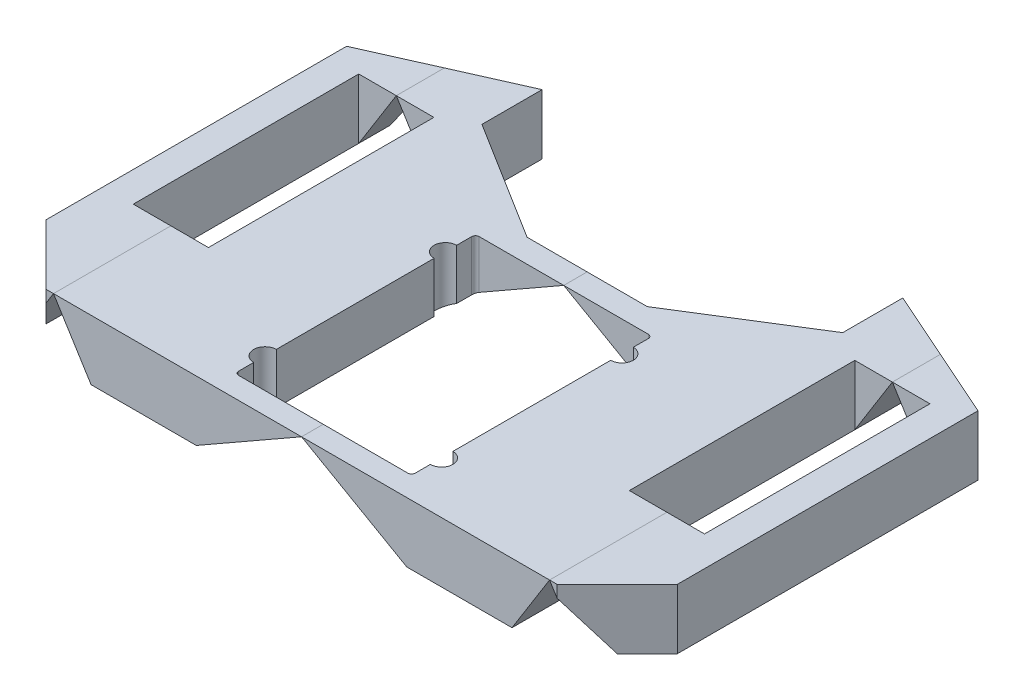
SolidWorks part; units mm, degrees
material "Polyurethane Foam Rigid"
ref_plane "Front Plane" through (0, 0, 0) normal (0, 0, 1) x (1, 0, 0)
ref_plane "Top Plane" through (0, 0, 0) normal (0, 1, 0) x (1, 0, 0)
ref_plane "Right Plane" through (0, 0, 0) normal (1, 0, 0) x (0, 0, -1)
sketch "Sketch1" plane through (0, 0, 0) normal (0, 1, 0) x (1, 0, 0)
  line L28 (52.9999, -138.966) -> (116.4999, -138.966) construction
  line L29 (52.9999, -138.966) -> (52.9999, -329.466) construction
  line L30 (52.9999, -329.466) -> (116.4999, -329.466) construction
  line L31 (116.4999, -138.966) -> (116.4999, -329.466) construction
  line L32 (472.0999, -138.966) -> (472.0999, -329.466) construction
  line L33 (535.5999, -329.466) -> (472.0999, -329.466) construction
  line L34 (535.5999, -138.966) -> (535.5999, -329.466) construction
  line L35 (535.5999, -138.966) -> (472.0999, -138.966) construction
  line L36 (446.6999, -123.7874) -> (345.0999, -187.2874) construction
  line L37 (446.6999, -72.9874) -> (446.6999, -123.7874) construction
  line L38 (560.9999, -123.7874) -> (446.6999, -72.9874) construction
  line L39 (560.9999, -377.7874) -> (560.9999, -123.7874) construction
  line L40 (510.1999, -428.5874) -> (560.9999, -377.7874) construction
  line L41 (78.3999, -428.5874) -> (510.1999, -428.5874) construction
  line L42 (78.3999, -428.5874) -> (27.5999, -377.7874) construction
  line L43 (27.5999, -123.8483) -> (27.5999, -375.907) construction
  line L44 (27.5999, -123.7874) -> (141.8999, -72.9874) construction
  line L45 (141.8999, -72.9874) -> (141.8999, -123.7874) construction
  line L46 (141.8999, -123.7874) -> (243.4999, -187.2874) construction
  line L47 (345.0999, -187.2874) -> (243.4999, -187.2874) construction
  line L48 (52.9999, -138.966) -> (116.4999, -138.966)
  line L49 (52.9999, -138.966) -> (52.9999, -329.466)
  line L50 (52.9999, -329.466) -> (116.4999, -329.466)
  line L51 (116.4999, -138.966) -> (116.4999, -329.466)
  line L52 (472.0999, -138.966) -> (472.0999, -329.466)
  line L53 (535.5999, -329.466) -> (472.0999, -329.466)
  line L54 (535.5999, -138.966) -> (535.5999, -329.466)
  line L55 (535.5999, -138.966) -> (472.0999, -138.966)
  line L56 (446.6999, -123.7874) -> (345.0999, -187.2874)
  line L57 (446.6999, -72.9874) -> (446.6999, -123.7874)
  line L58 (560.9999, -123.7874) -> (446.6999, -72.9874)
  line L59 (560.9999, -377.7874) -> (560.9999, -123.7874)
  line L60 (510.1999, -428.5874) -> (560.9999, -377.7874)
  line L61 (78.3999, -428.5874) -> (510.1999, -428.5874)
  line L62 (78.3999, -428.5874) -> (27.5999, -377.7874)
  line L63 (27.5999, -123.8483) -> (27.5999, -375.907)
  line L64 (27.5999, -123.7874) -> (141.8999, -72.9874)
  line L65 (141.8999, -72.9874) -> (141.8999, -123.7874)
  line L66 (141.8999, -123.7874) -> (243.4999, -187.2874)
  line L67 (345.0999, -187.2874) -> (243.4999, -187.2874)
  line L68 (27.5999, -377.7874) -> (27.5999, -375.907)
  line L69 (27.5999, -123.8483) -> (27.5999, -123.7874)
extrude "Boss-Extrude1" add sketch "Sketch1" against normal blind 50.8
sketch "Sketch2" plane through (0, 0, 0) normal (0, 0, 1) x (1, 0, 0)
  line L0 (294.2999, 0) -> (294.2999, 50000) construction
  line L1 (78.3999, 0) -> (510.1999, 0) construction
  line L14 (472.0999, 0) -> (535.5999, 0) construction
  line L15 (52.9999, 0) -> (116.4999, 0) construction
  line L16 (472.0999, 0) -> (535.5999, 0) construction
  line L17 (52.9999, 0) -> (116.4999, 0) construction
  line L18 (52.9999, 0) -> (52.9999, -50.8) construction
  line L19 (116.4999, 0) -> (116.4999, -50.8) construction
  line L20 (472.0999, 0) -> (472.0999, -50.8) construction
  line L21 (535.5999, 0) -> (535.5999, -50.8) construction
  line L22 (510.1999, -50.8) -> (560.9999, -50.8) construction
  line L23 (345.0999, 0) -> (243.4999, 0) construction
  line L24 (345.0999, 0) -> (243.4999, 0) construction
  line L25 (243.4999, 0) -> (243.4999, -50.8) construction
  line L26 (345.0999, 0) -> (345.0999, -50.8) construction
  line L27 (52.9999, -50.8) -> (84.7499, 0)
  line L28 (84.7499, 0) -> (116.4999, -50.8)
  line L29 (116.4999, -50.8) -> (52.9999, -50.8)
  line L30 (294.2999, 0) -> (205.3999, -50.8)
  line L31 (78.3999, -50.8) -> (510.1999, -50.8) construction
  line L32 (205.3999, -50.8) -> (383.1999, -50.8)
  line L33 (294.2999, 0) -> (383.1999, -50.8)
  line L34 (472.0999, -50.8) -> (535.5999, -50.8)
  line L35 (503.8499, 0) -> (472.0999, -50.8)
  line L36 (535.5999, -50.8) -> (503.8499, 0)
  point P4 (294.2999, 0)
  point P26 (294.2999, -50.8)
  dimension "D1" = 88.9
extrude "Cut-Extrude1" cut sketch "Sketch2" along normal through all
sketch "Sketch3" plane through (0, 0, 0) normal (0, 1, 0) x (1, 0, 0)
  line L1 (-27.9548, -40.3583) -> (618.3474, -40.3583)
  line L2 (-27.9548, -40.3583) -> (-27.9548, -468.3878)
  line L3 (-27.9548, -468.3878) -> (618.3474, -468.3878)
  line L4 (618.3474, -40.3583) -> (618.3474, -468.3878)
sketch "Sketch4" plane through (0, 0, 0) normal (0, 1, 0) x (1, 0, 0)
  line L0 (294.2999, -187.2874) -> (243.4999, -187.2874) construction
  line L1 (294.2999, -428.5874) -> (294.2999, -187.2874) construction
  line B0 (243.4999, -187.2874) -> (345.0999, -187.2874) construction
  line B1 (294.2999, -187.2874) -> (294.2999, 49812.7126) construction
  line B2 (368.9124, -222.9394) -> (368.9124, -210.2394)
  line B3 (368.9124, -375.3394) -> (368.9124, -241.9894)
  line B4 (368.9124, -407.0894) -> (368.9124, -394.3894)
  line B5 (222.8624, -410.2644) -> (365.7374, -410.2644)
  line B6 (219.6874, -394.3894) -> (219.6874, -407.0894)
  line B7 (219.6874, -241.9894) -> (219.6874, -375.3394)
  line B8 (219.6874, -210.2394) -> (219.6874, -222.9394)
  line B9 (365.7374, -207.0644) -> (222.8624, -207.0644)
  arc B10 (368.9124, -210.2394) -> (365.7374, -207.0644) centre (365.7374, -210.2394) ccw
  arc B11 (368.9124, -241.9894) -> (368.9124, -222.9394) centre (368.9124, -232.4644) ccw
  arc B12 (368.9124, -394.3894) -> (368.9124, -375.3394) centre (368.9124, -384.8644) ccw
  arc B13 (365.7374, -410.2644) -> (368.9124, -407.0894) centre (365.7374, -407.0894) ccw
  arc B14 (219.6874, -407.0894) -> (222.8624, -410.2644) centre (222.8624, -407.0894) ccw
  arc B15 (219.6874, -375.3394) -> (219.6874, -394.3894) centre (219.6874, -384.8644) ccw
  arc B16 (219.6874, -222.9394) -> (219.6874, -241.9894) centre (219.6874, -232.4644) ccw
  arc B17 (222.8624, -207.0644) -> (219.6874, -210.2394) centre (222.8624, -210.2394) ccw
sketch_block_instance "electricals_tub_cuttout-1"
sketch_block "electricals_tub_cuttout"
extrude "Cut-Extrude2" cut sketch "Sketch4" against normal through all
